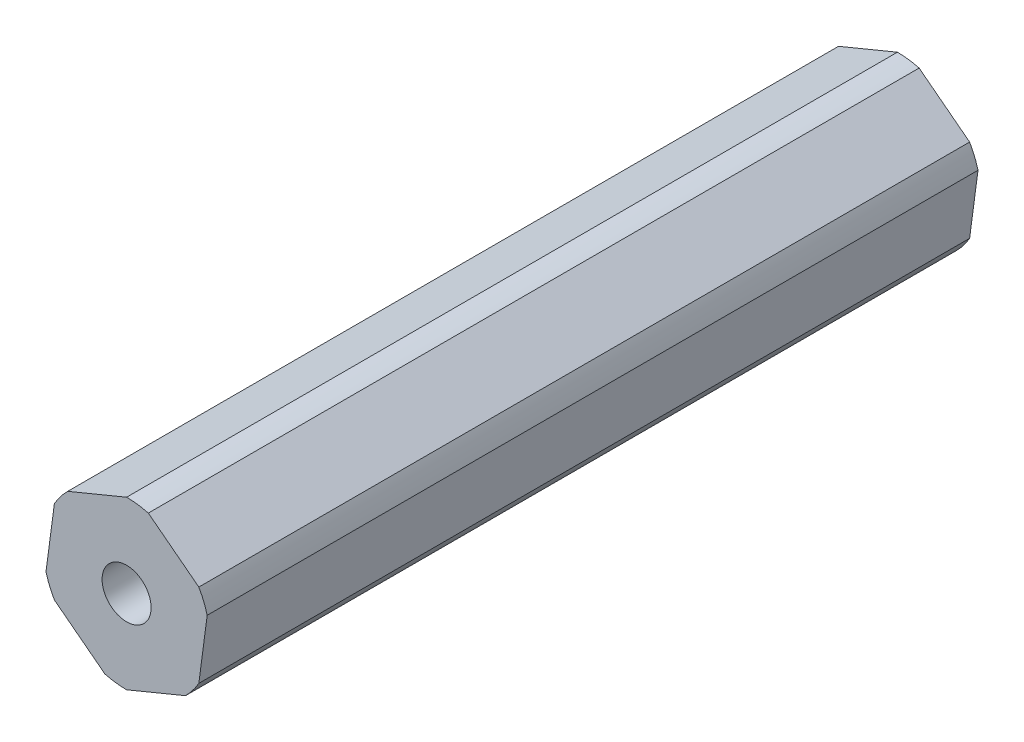
SolidWorks part; units mm, degrees
ref_plane "Front Plane" through (0, 0, 0) normal (0, 0, 1) x (1, 0, 0)
ref_plane "Top Plane" through (0, 0, 0) normal (0, 1, 0) x (1, 0, 0)
ref_plane "Right Plane" through (0, 0, 0) normal (1, 0, 0) x (0, 0, -1)
sketch "Sketch1" plane through (0, 0, 0) normal (0, 0, 1) x (1, 0, 0)
  line L1 (5.9502, 3.4353) -> (1.7899, 6.6335)
  line L2 (0, 6.8707) -> (-4.8498, 4.8668)
  line L3 (-5.9502, 3.4353) -> (-6.6397, -1.7666)
  line L4 (-5.9502, -3.4354) -> (-1.7899, -6.6335)
  line L5 (0, -6.8707) -> (4.8498, -4.8668)
  line L6 (5.9502, -3.4354) -> (6.6397, 1.7666)
  circle A0 centre (0, 0) radius 6.35 construction
  arc A1 (1.7899, 6.6335) -> (0, 6.8707) centre (0, 0) ccw
  arc A2 (6.6397, 1.7666) -> (5.9502, 3.4353) centre (0, 0) ccw
  arc A3 (4.8498, -4.8668) -> (5.9502, -3.4354) centre (0, 0) ccw
  arc A4 (-1.7899, -6.6335) -> (0, -6.8707) centre (0, 0) ccw
  arc A5 (-6.6397, -1.7666) -> (-5.9502, -3.4354) centre (0, 0) ccw
  arc A6 (-4.8498, 4.8668) -> (-5.9502, 3.4353) centre (0, 0) ccw
  point P3 (6.8403, -1.1583)
  point P4 (0, 0)
  point P6 (0, 0)
  dimension "D1" = 13.7414
  dimension ".5" = 12.7
extrude "Boss-Extrude1" add sketch "Sketch1" along normal blind 63.5
hole_wizard "#10-32 Tapped Hole1" positions "Sketch3" profile "Sketch4" tap size "#10-32" standard "ANSI Inch"
sketch "Sketch3" plane through (0, 0, 63.5) normal (0, 0, 1) x (1, 0, 0)
  point P0 (0, 0)
sketch "Sketch4" plane through (0, 0, 63.5) normal (1, 0, 0) x (0, -1, 0)
  line L0 (0, 0) -> (0, 13.2529)
  line L1 (0, 13.2529) -> (2.0193, 12.0396)
  line L2 (2.0193, 12.0396) -> (2.0193, 0)
  line L5 (2.0193, 0) -> (0, 0)
  line L10 (0, 13.2529) -> (-2.0193, 12.0396) construction
  line L11 (0, -6.35) -> (0, 107.95) construction
  dimension "Tap Drill Dia." = 4.0386
  dimension "Tap Drill Depth" = 12.0396
  dimension "Drill Angle" = 118
cosmetic thread "Hole Thread1"
hole_wizard "#10-32 Tapped Hole2" positions "Sketch6" profile "Sketch5" tap size "#10-32" standard "ANSI Inch"
sketch "Sketch6" plane through (0, 0, 0) normal (0, 0, -1) x (-1, 0, 0)
  point P0 (0, 0)
sketch "Sketch5" plane through (0, 0, 0) normal (1, 0, 0) x (0, 1, 0)
  line L0 (0, 0) -> (0, 13.2529)
  line L1 (0, 13.2529) -> (2.0193, 12.0396)
  line L2 (2.0193, 12.0396) -> (2.0193, 0)
  line L5 (2.0193, 0) -> (0, 0)
  line L10 (0, 13.2529) -> (-2.0193, 12.0396) construction
  line L11 (0, -6.35) -> (0, 107.95) construction
  dimension "Tap Drill Dia." = 4.0386
  dimension "Tap Drill Depth" = 12.0396
  dimension "Drill Angle" = 118
cosmetic thread "Hole Thread2" parameters "D1"=9.652, "D2"=4.826
